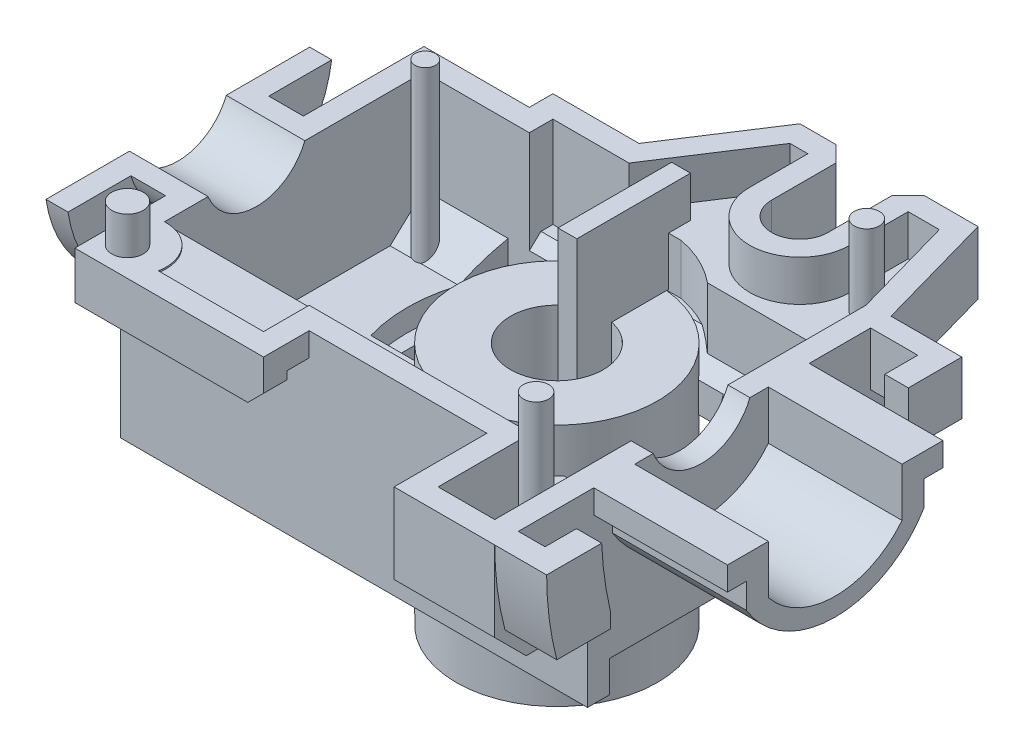
SolidWorks part; units mm, degrees
ref_plane "Front Plane" through (0, 0, 0) normal (0, 0, 1) x (1, 0, 0)
ref_plane "Top Plane" through (0, 0, 0) normal (0, 1, 0) x (1, 0, 0)
ref_plane "Right Plane" through (0, 0, 0) normal (1, 0, 0) x (0, 0, -1)
sketch "Sketch1" plane through (0, 0, 0) normal (0, 1, 0) x (1, 0, 0)
  line L1 (-14.85, 9.65) -> (14.85, 9.65)
  line L2 (-14.85, 9.65) -> (-14.85, -9.65)
  line L3 (-14.85, -9.65) -> (14.85, -9.65)
  line L4 (14.85, 9.65) -> (14.85, -9.65)
  line L5 (-14.85, 9.65) -> (14.85, -9.65) construction
  line L6 (-14.85, -9.65) -> (14.85, 9.65) construction
  point P0 (0, 0)
  dimension "D1" = 19.3
  dimension "D2" = 29.7
extrude "Boss-Extrude1" add sketch "Sketch1" along normal blind 9.9
sketch "Sketch2" plane through (0, 0, -9.65) normal (0, 0, -1) x (-1, 0, 0)
  line L1 (-14.85, 9.9) -> (3.65, 9.9)
  line L2 (-14.85, 9.9) -> (-14.85, 5.9)
  line L3 (-14.85, 5.9) -> (3.65, 5.9)
  line L4 (3.65, 9.9) -> (3.65, 5.9)
  dimension "D1" = 4
  dimension "D2" = 18.5
extrude "Boss-Extrude2" add sketch "Sketch2" along normal blind 7.7
sketch "Sketch4" plane through (0, 5.9, 0) normal (0, -1, 0) x (-1, 0, 0)
  line L0 (-14.85, 9.65) -> (-12.6797, 17.35)
  line L1 (-14.85, 17.35) -> (3.65, 17.35) construction
  line L2 (-12.6797, 17.35) -> (-14.85, 17.35)
  line L3 (-14.85, 17.35) -> (-14.85, 9.65)
  line L4 (-14.85, 9.65) -> (3.65, 9.65) construction
  line L5 (-8.239, 12.25) -> (-8.239, 17.35)
  line L6 (-4.661, 12.25) -> (-4.661, 17.35)
  line L7 (-8.239, 17.35) -> (-4.661, 17.35)
  line L9 (-1.361, 17.35) -> (3.65, 9.65)
  line L10 (3.65, 9.65) -> (3.65, 17.35)
  line L11 (3.65, 17.35) -> (-1.361, 17.35)
  arc A0 (-8.239, 12.25) -> (-4.661, 12.25) centre (-6.45, 12.25) ccw
  dimension "D1" = 8
  dimension "D2" = 2.6
  dimension "D3" = 8.4
  dimension "D4" = 3.3
extrude "Cut-Extrude1" cut sketch "Sketch4" against normal through all
sketch "Sketch5" plane through (0, 5.9, 0) normal (0, -1, 0) x (1, 0, 0)
  line L0 (14.85, -9.65) -> (-3.65, -9.65) construction
  line L1 (1.5322, -9.65) -> (-8.15, -9.65)
  line L3 (1.5322, -11.15) -> (-8.15, -11.15)
  line L4 (-8.15, -9.65) -> (-8.15, -11.15)
  line L5 (-14.85, -9.65) -> (-14.85, 9.65) construction
  line L6 (1.5322, -9.65) -> (5.0522, -9.65)
  arc A0 (1.5322, -11.15) -> (5.0522, -9.65) centre (0.0685, -2.835) ccw
  dimension "D1" = 1.5
  dimension "D2" = 6.7
  dimension "D3" = 9.6822
  dimension "D4" = 3.52
extrude "Boss-Extrude3" add sketch "Sketch5" along normal blind 3.2
sketch "Sketch6" plane through (0, 5.9, 0) normal (0, 1, 0) x (1, 0, 0)
  line L0 (-2.6738, 11.15) -> (-3.65, 9.65)
  line L1 (-3.65, 9.65) -> (-8.15, 9.65)
  line L2 (-8.15, 9.65) -> (-8.15, 11.15)
  line L3 (-8.15, 11.15) -> (-2.6738, 11.15)
extrude "Boss-Extrude4" add sketch "Sketch6" along normal up to surface (4 mm away) up to face at (3.2901, 9.9, -9.251)
sketch "Sketch7" plane through (0, 0, -9.65) normal (0, 0, -1) x (-1, 0, 0)
  line L0 (14.85, 9.9) -> (14.85, 0) construction
  line L1 (8.15, 9.9) -> (14.85, 9.9) construction
  circle A0 centre (11.55, 5.8) radius 0.95
  dimension "D1" = 1.9
  dimension "D2" = 3.3
  dimension "D3" = 4.1
extrude "Boss-Extrude5" add sketch "Sketch7" along normal blind 2.9
sketch "Sketch9" plane through (14.85, 0, 0) normal (1, 0, 0) x (0, 0, -1)
  line L0 (-9.65, 9.9) -> (9.65, 9.9) construction
  line L1 (4.45, 9.9) -> (1.85, 9.9)
  line L2 (4.45, 9.9) -> (4.45, 8.4)
  line L3 (4.45, 8.4) -> (3.25, 8.4)
  line L4 (1.85, 9.9) -> (1.85, 8.4)
  line L5 (9.65, 9.9) -> (9.65, 5.9) construction
  line L6 (-2.4, 9.9) -> (-2.4, 0) construction
  line L8 (1.85, 8.4) -> (1.85, 6.8)
  line L10 (3.25, 8.4) -> (3.25, 6.8)
  line L12 (-9.25, 8.4) -> (-8.05, 8.4)
  line L13 (-6.65, 9.9) -> (-6.65, 8.4)
  line L14 (-9.25, 9.9) -> (-6.65, 9.9)
  line L15 (-9.25, 9.9) -> (-9.25, 8.4)
  line L17 (-8.05, 8.4) -> (-8.05, 6.8)
  line L19 (-6.65, 8.4) -> (-6.65, 6.8)
  line L20 (-9.65, 0) -> (9.65, 0) construction
  arc A0 (3.25, 6.8) -> (-8.05, 6.8) centre (-2.4, 10.1879) cw
  arc A1 (1.85, 6.8) -> (-6.65, 6.8) centre (-2.4, 10.1879) cw
  point P22 (-2.4, 3.6)
  dimension "D1" = 2.6
  dimension "D2" = 1.5
  dimension "D3" = 5.2
  dimension "D4" = 1.4
  dimension "D5" = 1.6
  dimension "D6" = 2.4
  dimension "D7" = 3.6
extrude "Boss-Extrude6" add sketch "Sketch9" along normal blind 8.5
sketch "Sketch11" plane through (0, 0, 9.65) normal (0, 0, 1) x (1, 0, 0)
  line L1 (-14.85, 9.9) -> (-2.85, 9.9)
  line L2 (-14.85, 9.9) -> (-14.85, 6.9)
  line L3 (-14.85, 6.9) -> (-2.85, 6.9)
  line L4 (-2.85, 9.9) -> (-2.85, 6.9)
  dimension "D1" = 12
  dimension "D2" = 3
extrude "Boss-Extrude7" add sketch "Sketch11" along normal blind 2.9
sketch "Sketch12" plane through (0, 6.9, 0) normal (0, -1, 0) x (1, 0, 0)
  line L0 (-14.85, 12.55) -> (-2.85, 12.55) construction
  line L1 (-2.85, 9.65) -> (-11.83, 9.65)
  line L2 (-2.85, 9.65) -> (-2.85, 11.05)
  line L3 (-2.85, 11.05) -> (-11.83, 11.05)
  line L4 (-11.83, 9.65) -> (-11.83, 11.05)
  dimension "D1" = 8.98
  dimension "D2" = 1.5
extrude "Cut-Extrude2" cut sketch "Sketch12" against normal blind 1.5
sketch "Sketch13" plane through (0, 6.9, 0) normal (0, -1, 0) x (1, 0, 0)
  line L0 (-14.85, 12.55) -> (-14.85, 9.65) construction
  line L1 (-14.85, 9.65) -> (-11.83, 9.65) construction
  circle A0 centre (-13.35, 10.7) radius 1.05
  point P4 (0, 0)
  dimension "D1" = 2.1
  dimension "D2" = 1.5
  dimension "D3" = 1.05
extrude "Cut-Extrude3" cut sketch "Sketch13" against normal blind 2.3
sketch "Sketch14" plane through (0, 9.9, 0) normal (0, 1, 0) x (1, 0, 0)
  line L1 (-14.85, 9.65) -> (-14.85, -12.55) construction
  line L2 (-2.85, -12.55) -> (-14.85, -12.55) construction
  circle A0 centre (-13.35, -10.7) radius 1
  dimension "D1" = 2
  dimension "D2" = 1.5
  dimension "D3" = 1.85
extrude "Boss-Extrude8" add sketch "Sketch14" along normal blind 2.4
sketch "Sketch15" plane through (0, 0, 9.65) normal (0, 0, 1) x (1, 0, 0)
  line L1 (14.85, 2.8) -> (8.45, 2.8)
  line L2 (14.85, 2.8) -> (14.85, 9.9)
  line L3 (14.85, 9.9) -> (8.45, 9.9)
  line L4 (8.45, 2.8) -> (8.45, 9.9)
  point P5 (8.45, 0)
  point P6 (0, 0)
  point P7 (0, 0)
  dimension "D1" = 7.1
  dimension "D2" = 6.4
extrude "Boss-Extrude9" add sketch "Sketch15" along normal blind 5.9
sketch "Sketch16" plane through (14.85, 0, 0) normal (1, 0, 0) x (0, 0, -1)
  line L0 (-15.55, 9.9) -> (-12.05, 9.9)
  line L1 (-15.55, 9.9) -> (-9.25, 9.9) construction
  line L2 (-14.9, 4.9) -> (-11.5, 4.9)
  line L3 (-15.55, 2.8) -> (-15.55, 9.9) construction
  line L4 (-12.05, 9.9) -> (-12.05, 7.7386) construction
  line L5 (-11.5, 4.9) -> (-11.5, 5.9)
  spline S0 degree 2 poles (-14.9, 4.9) (-15.5427, 7.3513) (-15.55, 9.9) knots 0 0 0 1 1 1
  spline S1 degree 2 poles (-11.5, 5.9) (-11.9642, 7.8708) (-12.05, 9.9) knots 0 0 0 1 1 1
  point P14 (-15.2337, 6.1931)
  point P15 (-11.7618, 7.1874)
  point P16 (-15.2473, 6.4849)
  dimension "D1" = 3.5
  dimension "D2" = 3.4
  dimension "D3" = 0.65
  dimension "D4" = 5
  dimension "D5" = 1
extrude "Boss-Extrude11" add sketch "Sketch16" along normal blind 3.3
sketch "Sketch17" plane through (0, 9.9, 0) normal (0, 1, 0) x (1, 0, 0)
  line L0 (18.15, -11.5) -> (14.85, -11.5) construction
  line L1 (14.85, -14.05) -> (16.55, -14.05)
  line L2 (14.85, -14.05) -> (14.85, -11.5)
  line L3 (14.85, -11.5) -> (16.55, -11.5)
  line L4 (16.55, -14.05) -> (16.55, -11.5)
  line L5 (18.15, -15.55) -> (14.85, -15.55) construction
  line L6 (18.15, -12.05) -> (18.15, -15.55) construction
  dimension "D1" = 1.5
  dimension "D2" = 1.6
extrude "Cut-Extrude4" cut sketch "Sketch17" against normal blind 4
sketch "Sketch18" plane through (14.85, 0, 0) normal (1, 0, 0) x (0, 0, -1)
  line L1 (9.65, 9.9) -> (8.35, 9.9)
  line L2 (9.65, 9.9) -> (9.65, 6.5)
  line L3 (9.65, 6.5) -> (8.35, 6.5)
  line L4 (8.35, 9.9) -> (8.35, 6.5)
  dimension "D1" = 3.4
  dimension "D2" = 1.3
extrude "Boss-Extrude12" add sketch "Sketch18" along normal blind 3
sketch "Sketch19" plane through (17.85, 0, 0) normal (1, 0, 0) x (0, 0, -1)
  line L1 (9.65, 9.9) -> (6.25, 9.9)
  line L2 (9.65, 9.9) -> (9.65, 6.5)
  line L3 (9.65, 6.5) -> (6.25, 6.5)
  line L4 (6.25, 9.9) -> (6.25, 6.5)
  dimension "D1" = 3.4
extrude "Boss-Extrude13" add sketch "Sketch19" along normal blind 1.5
ref_plane "Plane1" through (0, 0, 2.4) normal (0, 0, 1) x (1, 0, 0)
sketch "Sketch21" plane through (-14.85, 0, 0) normal (-1, 0, 0) x (0, 0, 1)
  line L0 (2.4, -7.7761) -> (2.4, 7.7761) construction
  line L1 (-9.65, 9.9) -> (12.55, 9.9) construction
  line L3 (6.7834, 9.9) -> (5.477, 9.9)
  line L4 (-0.677, 9.9) -> (-1.9834, 9.9)
  arc A0 (-0.677, 9.9) -> (5.477, 9.9) centre (2.4, 11.12) ccw
  arc A1 (-1.9834, 9.9) -> (6.7834, 9.9) centre (2.4, 11.12) ccw
  dimension "D1" = 6.62
  dimension "D3" = 9.1
  dimension "D2" = 1.22
extrude "Boss-Extrude14" add sketch "Sketch21" along normal blind 2.2
sketch "Sketch22" plane through (-17.05, 0, 0) normal (-1, 0, 0) x (0, 0, 1)
sketch "Sketch25" plane through (-17.05, 0, 0) normal (-1, 0, 0) x (0, 0, 1)
  line L0 (-1.9834, 9.9) -> (-5.9834, 9.9)
  line L1 (-9.65, 9.9) -> (-1.9834, 9.9) construction
  line L2 (6.7834, 9.9) -> (10.7834, 9.9)
  line L3 (6.7834, 9.9) -> (12.55, 9.9) construction
  line L4 (-1.9834, 9.9) -> (-0.677, 9.9)
  line L5 (5.477, 9.9) -> (6.7834, 9.9)
  arc A0 (-5.9834, 9.9) -> (10.7834, 9.9) centre (2.4, 11.12) ccw
  arc A1 (-0.677, 9.9) -> (5.477, 9.9) centre (2.4, 11.12) ccw
  dimension "D1" = 4
extrude "Boss-Extrude15" add sketch "Sketch25" along normal blind 1.4
sketch "Sketch27" plane through (0, 0, 0) normal (0, -1, 0) x (1, 0, 0)
  line L0 (14.85, 9.65) -> (14.85, -9.65) construction
  line L1 (-14.85, 9.65) -> (14.85, 9.65)
  line L2 (-14.85, 9.65) -> (-14.85, 8.25)
  line L3 (-14.85, 8.25) -> (14.85, 8.25)
  line L4 (14.85, 9.65) -> (14.85, 8.25)
  dimension "D1" = 1.4
extrude "Boss-Extrude16" add sketch "Sketch27" along normal blind 2
chamfer "Chamfer1" distance 3 distance2 2.8 1 edges at (0, 0, -9.65) first distance on face at (0, 0, -0.7)
shell "Shell2" thickness 1.4 removed face at (3.3397, 9.9, 0.1923)
sketch "Sketch28" plane through (0, 0, 0) normal (0, -1, 0) x (1, 0, 0)
  line L0 (14.85, -9.65) -> (-14.85, -9.65) construction
  circle A0 centre (0, -3.25) radius 6.4
  circle A1 centre (0, -3.25) radius 5
  dimension "D1" = 12.8
  dimension "D3" = 1.4
  dimension "D2" = 6.4
sketch "Sketch31" plane through (0, 0, 0) normal (0, -1, 0) x (1, 0, 0)
  line L0 (-3.995, -8.25) -> (-8.095, -8.25)
  line L1 (14.85, -9.65) -> (-14.85, -9.65) construction
  line L2 (0, -14.25) -> (0, 3.15) construction
  line L3 (-5.8026, -0.55) -> (-9.1235, -0.55)
  line L4 (4.7403, 1.05) -> (8.4876, 1.05)
  line L5 (4.9143, -7.35) -> (8.586, -7.35)
  line L6 (0, 6.2647) -> (0, 1013.4261) construction
  arc A0 (4.9143, -7.35) -> (4.7403, 1.05) centre (0, -3.25) ccw
  arc A1 (8.586, -7.35) -> (8.4876, 1.05) centre (0, -3.25) ccw
  arc A2 (-9.1235, -0.55) -> (-8.095, -8.25) centre (0, -3.25) ccw
  arc A3 (-5.8026, -0.55) -> (-3.995, -8.25) centre (0, -3.25) ccw
  circle A4 centre (0, -3.25) radius 6.4 construction
  point P1 (4.7403, 1.05)
  point P13 (8.6787, 0.65)
  point P17 (8.586, -7.35)
  point P18 (0, 0)
  dimension "D1" = 1.4
  dimension "D2" = 4.1
  dimension "D3" = 7.7
  dimension "D5" = 2.3
  dimension "D6" = 8.4
extrude "Cut-Extrude5" cut sketch "Sketch31" against normal through all
extrude "Boss-Extrude17" add sketch "Sketch28" along normal blind 11.3
sketch "Sketch32" plane through (0, 0, 0) normal (0, -1, 0) x (1, 0, 0)
  circle A0 centre (0, -3.25) radius 5
extrude "Cut-Extrude6" cut sketch "Sketch32" against normal through all
sketch "Sketch33" plane through (0, 1.4, 0) normal (0, 1, 0) x (1, 0, 0)
  circle A1 centre (0, 3.25) radius 6.4
extrude "Boss-Extrude18" add sketch "Sketch33" along normal blind 2.8
sketch "Sketch34" plane through (0, 4.2, 0) normal (0, 1, 0) x (1, 0, 0)
  circle A0 centre (0, 3.25) radius 2.95
  dimension "D1" = 5.9
extrude "Cut-Extrude7" cut sketch "Sketch34" against normal through all
sketch "Sketch35" plane through (0, 7.3, 0) normal (0, 1, 0) x (1, 0, 0)
  line L0 (0, 0.6731) -> (0, 4.4957) construction
  line L1 (-0.6, 11.15) -> (0.6, 11.15)
  line L2 (-0.6, 11.15) -> (-0.6, 3.92)
  line L3 (-0.6, 3.92) -> (0.6, 3.92)
  line L4 (0.6, 11.15) -> (0.6, 3.92)
  line L5 (2.95, 3.25) -> (-2.95, 3.25) construction
  circle A0 centre (0, 3.25) radius 2.95 construction
  dimension "D1" = 1.2
  dimension "D2" = 0.6
  dimension "D3" = 0.67
extrude "Boss-Extrude19" add sketch "Sketch35" along normal up to surface (2.6 mm away) up to face at (1.3934, 9.9, -3.1011)
sketch "Sketch36" plane through (0, 4.2, 0) normal (0, 1, 0) x (1, 0, 0)
  line L0 (-6.75, 9.75) -> (1.4043, 9.75) construction
  line L1 (-0.6, 3.92) -> (0.6, 3.92)
  line L2 (-0.6, 3.92) -> (-0.6, 9.75)
  line L3 (-0.6, 9.75) -> (0.6, 9.75)
  line L4 (0.6, 3.92) -> (0.6, 9.75)
extrude "Boss-Extrude20" add sketch "Sketch36" along normal up to next
sketch "Sketch38" plane through (0, 4.2, 0) normal (0, -1, 0) x (1, 0, 0)
  line L0 (-0.6, -3.92) -> (0.6, -3.92)
  line L1 (0.6, -3.92) -> (0.6, -6.1383)
  line L2 (-0.6, -3.92) -> (-0.6, -6.1383)
  arc A0 (-0.6, -6.1383) -> (0.6, -6.1383) centre (0, -3.25) ccw
sketch "Sketch39" plane through (0, 0, 0) normal (0, 1, 0) x (1, 0, 0)
  circle A0 centre (0, 3.25) radius 6.4
  circle A1 centre (0, 3.25) radius 2.95
extrude "Boss-Extrude22" add sketch "Sketch39" along normal up to next
extrude "Boss-Extrude27" add sketch "Sketch38" along normal blind 4.2
sketch "Sketch40" plane through (0, 0, 0) normal (0, -1, 0) x (1, 0, 0)
  line L0 (6.992, -0.0761) -> (10.492, -0.0761)
  line L2 (6.486, -7.35) -> (9.986, -7.35)
  arc A1 (6.992, -0.0761) -> (6.486, -7.35) centre (0.0019, -3.2444) cw
  arc A2 (10.492, -0.0761) -> (9.986, -7.35) centre (0.1025, -3.0079) cw
  point P4 (6.486, -7.2067)
  point P7 (0, 0)
  point P8 (9.986, -7.2067)
  point P12 (10.257, -0.1415)
  point P15 (7.0824, -0.2989)
  dimension "D4" = 3.5
  dimension "D1" = 3.5
extrude "Boss-Extrude28" add sketch "Sketch40" along normal blind 2.9
ref_plane "Plane2" through (0, 0, 0) normal (1, 0, 0) x (0, 0, -1)
mirror "Mirror1" about plane through (0, 0, 0) normal (1, 0, 0) of "Boss-Extrude28"
sketch "Sketch45" plane through (0, 0, -7.35) normal (0, 0, -1) x (-1, 0, 0)
  line L0 (9.986, -2.9) -> (9.986, 0) construction
  line L1 (6.486, 0) -> (8.586, 0)
  line L2 (6.486, 0) -> (6.486, -1.5)
  line L3 (6.486, -1.5) -> (8.586, -1.5)
  line L4 (8.586, 0) -> (8.586, -1.5)
  line L5 (6.486, -2.9) -> (9.986, -2.9) construction
  dimension "D1" = 1.4
  dimension "D2" = 1.4
extrude "Cut-Extrude9" cut sketch "Sketch45" against normal blind 6.7
sketch "Sketch46" plane through (0, 0, -0.0761) normal (0, 0, 1) x (1, 0, 0)
  line L0 (10.492, -2.9) -> (6.992, -2.9) construction
  line L1 (6.992, 0) -> (9.092, 0)
  line L2 (6.992, 0) -> (6.992, -1.5)
  line L3 (6.992, -1.5) -> (9.092, -1.5)
  line L4 (9.092, 0) -> (9.092, -1.5)
  line L5 (10.492, -2.9) -> (10.492, 0) construction
  dimension "D1" = 1.4
  dimension "D2" = 1.4
extrude "Cut-Extrude10" cut sketch "Sketch46" against normal blind 6.7
sketch "Sketch49" plane through (0, 7.3, 0) normal (0, 1, 0) x (1, 0, 0)
  line L0 (13.45, 8.25) -> (4.5717, 8.25) construction
  circle A0 centre (11.2085, 11.75) radius 0.8
  point P4 (11.2085, 11.75)
  dimension "D1" = 1.6
  dimension "D2" = 3.5
extrude "Boss-Extrude41" add sketch "Sketch49" along normal blind 5.1
sketch "Sketch50" plane through (0, 4.2, 0) normal (0, 1, 0) x (1, 0, 0)
  line L0 (9.85, -8.25) -> (13.45, -8.25) construction
  circle A0 centre (11.5294, -9.6) radius 0.8
  point P4 (11.5294, -9.6)
  dimension "D1" = 1.6
  dimension "D2" = 1.35
extrude "Boss-Extrude42" add sketch "Sketch50" along normal blind 9.5
sketch "Sketch51" plane through (0, 1.4, 0) normal (0, 1, 0) x (1, 0, 0)
  line L0 (-13.45, 6.0982) -> (-13.45, -8.25) construction
  line L1 (-8.095, 8.25) -> (-13.45, 8.25) construction
  circle A0 centre (-11.8, 6.68) radius 0.65
  dimension "D1" = 1.3
  dimension "D2" = 1.65
  dimension "D3" = 1.57
extrude "Boss-Extrude43" add sketch "Sketch51" along normal blind 10.8
ref_plane "Plane3" through (0, 0, 0) normal (0, 1, 0) x (1, 0, 0)
sketch "Sketch54" plane through (0, 0, 0) normal (0, 1, 0) x (1, 0, 0)
  line L0 (6.992, 6.4126) -> (6.486, 7.35)
  line L1 (6.486, 7.35) -> (8.586, 7.35)
  line L2 (8.586, 7.35) -> (8.8124, 6.7761)
  line L3 (6.992, 6.7761) -> (9.092, 6.7761) construction
  line L4 (8.8124, 6.7761) -> (6.992, 6.7761)
  line L5 (6.992, 6.7761) -> (6.992, 6.4126)
extrude "Boss-Extrude44" add sketch "Sketch54" along normal up to surface (2.0328 mm away) up to face at (7.5618, 2.8859, -7.6902)
chamfer "Chamfer2" distance 1 angle 45 2 edges at (4.661, 7.9, -17.35) (8.239, 7.9, -17.35)
sketch "Sketch55" plane through (-14.85, 0, 0) normal (-1, 0, 0) x (0, 0, 1)
  line L0 (-0.677, 9.9) -> (5.477, 9.9)
  arc A0 (-0.677, 9.9) -> (5.477, 9.9) centre (2.4, 11.12) ccw
extrude "Cut-Extrude11" cut sketch "Sketch55" against normal through all
chamfer "Chamfer3" distance 1 angle 45 1 edges at (-2.85, 6.9, 11.8)
chamfer "Chamfer4" distance 2 angle 45 1 edges at (11.65, 2.8, 15.55)
